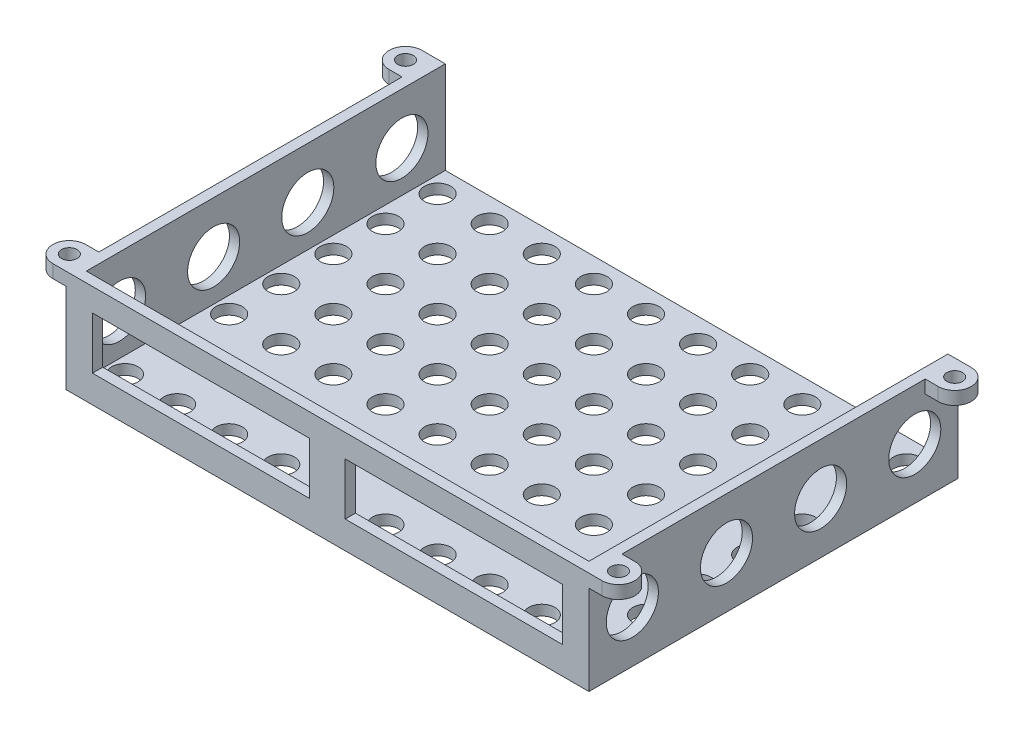
SolidWorks part; units mm, degrees
other "Markup2"
sketch "Sketch32" plane through (-159.4724, 0, 108) normal (-0.262, -0.0774, 0.962) x (0.8638, -0.4632, 0.198)
ref_plane "Front Plane" through (0, 0, 0) normal (0, 0, 1) x (1, 0, 0)
ref_plane "Top Plane" through (0, 0, 0) normal (0, 1, 0) x (1, 0, 0)
ref_plane "Right Plane" through (0, 0, 0) normal (1, 0, 0) x (0, 0, -1)
sketch "Sketch1" plane through (0, 0, 0) normal (0, 1, 0) x (1, 0, 0)
  line L1 (0, 0) -> (-153, 0)
  line L2 (0, 0) -> (0, -108)
  line L3 (0, -108) -> (-153, -108)
  line L4 (-153, 0) -> (-153, -108)
extrude "Boss-Extrude1" add sketch "Sketch1" along normal blind 30 contours L1 L4 L3 L2
shell "Shell1" thickness 3 removed face at (-76.5, 30, 54)
sketch "Sketch7" plane through (0, 30, 0) normal (0, 1, 0) x (1, 0, 0)
  line L0 (-156.81, 0) -> (-153, 0)
  line L1 (-153, 0) -> (-153, -9.652)
  line L2 (-153, 0) -> (-153, -108) construction
  line L3 (-153, -9.652) -> (-156.81, -9.652)
  circle A0 centre (-156.81, -4.826) radius 2.286
  arc A2 (-156.81, 0) -> (-156.81, -9.652) centre (-156.81, -4.826) ccw
  dimension "D1" = 2.54
  dimension "D3" = 4.572
  dimension "D2" = 3.81
extrude "Boss-Extrude7" add sketch "Sketch7" against normal blind 3.81
sketch "Sketch24" plane through (0, 0, 0) normal (0, -1, 0) x (1, 0, 0)
  circle A0 centre (-8.0557, 7.0511) radius 3.8453
extrude "Cut-Extrude8" cut sketch "Sketch24" against normal blind 25.4
pattern_linear "LPattern5" count 10 spacing 15.24 along (-1, 0, 0) of "Cut-Extrude8"
pattern_linear "LPattern6" count 10 spacing 15.24 along (0, 0, 1) of "LPattern5"
sketch "Sketch27" plane through (0, 0, 3) normal (0, 0, 1) x (1, 0, 0)
  line L0 (-3, 3) -> (-3, 30)
  line L1 (-3, 30) -> (-3, 3) construction
  line L2 (-3, 30) -> (-150, 30)
  line L3 (-150, 30) -> (-150, 3)
  line L4 (-150, 3) -> (-3, 3)
extrude "Cut-Extrude10" cut sketch "Sketch27" against normal blind 5.08
sketch "Sketch30" plane through (0, 0, 0) normal (1, 0, 0) x (0, 0, -1)
  line L0 (0, 30) -> (0, 0) construction
  line L1 (-108, 30) -> (-108, 0) construction
  circle A0 centre (-12.7, 15) radius 7.62
  circle A1 centre (-40.2333, 15) radius 7.62
  circle A2 centre (-67.7667, 15) radius 7.62
  circle A3 centre (-95.3, 15) radius 7.62
  point P13 (0, 15)
  dimension "D2" = 15.24
  dimension "D3" = 12.7
  dimension "D4" = 12.7
  dimension "D1" = 4
extrude "Cut-Extrude14" cut sketch "Sketch30" against normal blind 7.62
ref_plane "Plane1" through (0, 0, 54) normal (0, 0, -1) x (-1, 0, 0)
ref_plane "Plane2" through (-76.5, 0, 0) normal (-1, 0, 0) x (0, 0, 1)
mirror "Mirror1" about plane through (0, 0, 54) normal (0, 0, -1) of "Boss-Extrude7"
mirror "Mirror2" about plane through (-76.5, 0, 0) normal (-1, 0, 0) of "Mirror1"
mirror "Mirror4" about plane through (-76.5, 0, 0) normal (-1, 0, 0) of "Cut-Extrude14"
sketch "Sketch33" plane through (0, 0, 108) normal (0, 0, 1) x (1, 0, 0)
  line L0 (-145.2079, 8.0466) -> (-81.7079, 8.0466)
  line L2 (-145.2079, 8.0466) -> (-145.2079, 23.2866)
  line L3 (-145.2079, 23.2866) -> (-81.7079, 23.2866)
  line L4 (-81.7079, 23.2866) -> (-81.7079, 8.0466)
  dimension "D1" = 15.24
  dimension "D2" = 63.5
  dimension "D3" = 63.5
  dimension "D4" = 15.24
extrude "Cut-Extrude16" cut sketch "Sketch33" against normal blind 5.08 contours L3 L4 L0 L2
mirror "Mirror6" about plane through (-76.5, 0, 0) normal (-1, 0, 0) of "Cut-Extrude16"
